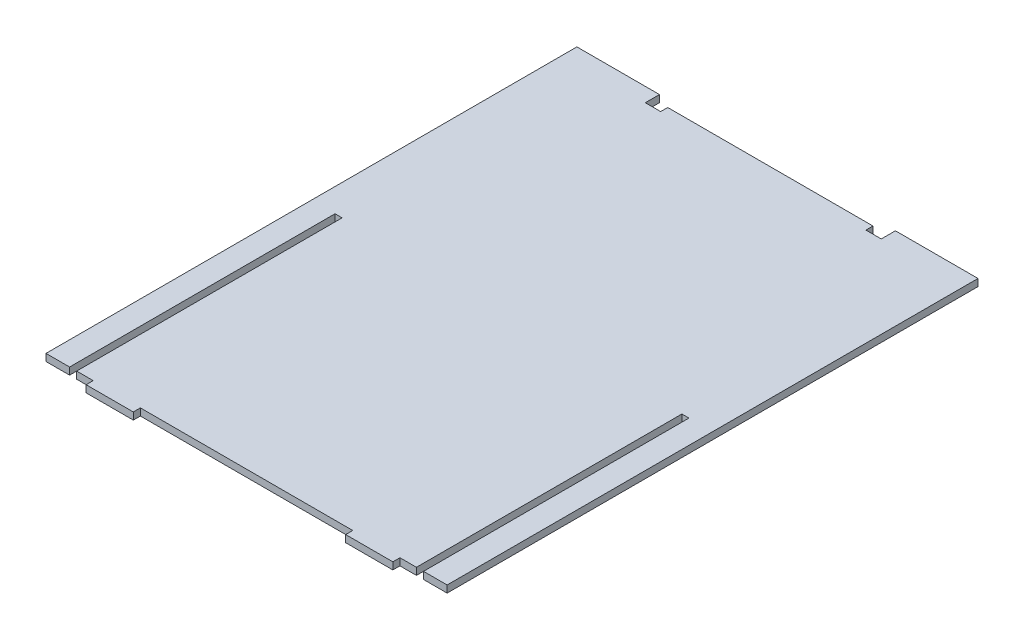
SolidWorks part; units mm, degrees
ref_plane "Front Plane" through (0, 0, 0) normal (0, 0, 1) x (1, 0, 0)
ref_plane "Top Plane" through (0, 0, 0) normal (0, 1, 0) x (1, 0, 0)
ref_plane "Right Plane" through (0, 0, 0) normal (1, 0, 0) x (0, 0, -1)
sketch "Sketch1" plane through (0, 0, 0) normal (0, 1, 0) x (1, 0, 0)
  line L0 (300, 0) -> (300, -6)
  line L2 (0, 0) -> (0, 450)
  line L3 (0, 450) -> (340, 450)
  line L4 (340, 0) -> (340, 450)
  line L5 (300, -6) -> (260, -6)
  line L6 (260, -6) -> (260, 0)
  line L7 (40, 0) -> (40, -6)
  line L8 (40, -6) -> (80, -6)
  line L9 (80, -6) -> (80, 0)
  line L10 (40, 0) -> (0, 0)
  line L11 (80, 0) -> (260, 0)
  line L12 (300, 0) -> (340, 0)
  point P11 (80, -3)
  dimension "D1" = 340
  dimension "D2" = 450
  dimension "D3" = 40
  dimension "D4" = 6
  dimension "D5" = 40
  dimension "D6" = 180
extrude "Boss-Extrude1" add sketch "Sketch1" along normal blind 6
sketch "Sketch2" plane through (0, 6, 0) normal (0, 1, 0) x (1, 0, 0)
  line L1 (20, 0) -> (26, 0)
  line L2 (20, 0) -> (20, 225)
  line L3 (20, 225) -> (26, 225)
  line L4 (26, 0) -> (26, 225)
  line L5 (0, 450) -> (0, 0) construction
  line L6 (0, 0) -> (40, 0) construction
  line L7 (0, 0) -> (40, 0) construction
  dimension "D1" = 225
  dimension "D2" = 6
  dimension "D3" = 20
extrude "Cut-Extrude1" cut sketch "Sketch2" against normal blind 6
pattern_linear "LPattern1" count 2 spacing 294 along (1, 0, 0) of "Cut-Extrude1"
sketch "Sketch3" plane through (0, 6, 0) normal (0, 1, 0) x (1, 0, 0)
  line L3 (340, 450) -> (0, 450) construction
  line L4 (70, 450) -> (270, 450)
  line L18 (70, 450) -> (70, 438)
  line L19 (70, 438) -> (83, 438)
  line L20 (83, 438) -> (83, 444)
  line L21 (270, 450) -> (270, 438)
  line L22 (270, 438) -> (257, 438)
  line L23 (257, 438) -> (257, 444)
  line L24 (83, 444) -> (257, 444)
  line L25 (0, 450) -> (0, 0) construction
  dimension "D1" = 200
  dimension "D2" = 12
  dimension "D3" = 13
  dimension "D4" = 6
  dimension "D5" = 70
extrude "Cut-Extrude2" cut sketch "Sketch3" against normal blind 6
